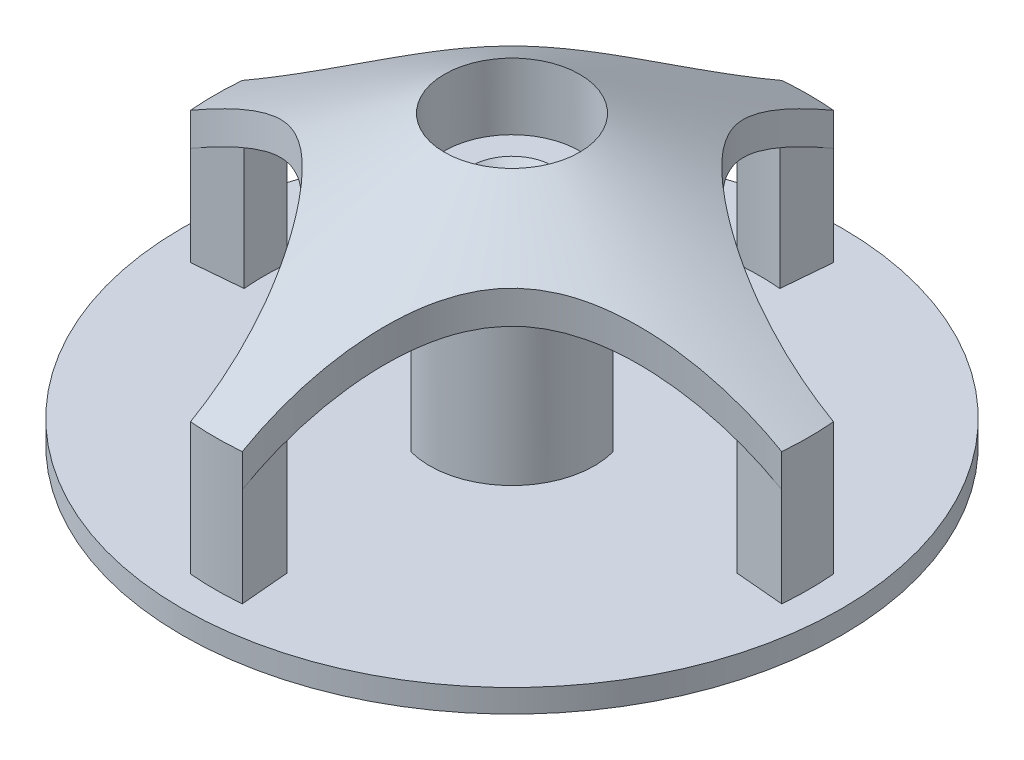
SolidWorks part; units mm, degrees
ref_plane "Front Plane" through (0, 0, 0) normal (0, 0, 1) x (1, 0, 0)
ref_plane "Top Plane" through (0, 0, 0) normal (0, 1, 0) x (1, 0, 0)
ref_plane "Right Plane" through (0, 0, 0) normal (1, 0, 0) x (0, 0, -1)
sketch "Sketch1" plane through (0, 0, 0) normal (0, 1, 0) x (1, 0, 0)
  circle A0 centre (0, 0) radius 127
  dimension "D1" = 254
extrude "Base of base" add sketch "Sketch1" along normal blind 8.89
ref_plane "Top Platform Offset" through (0, 46.99, 0) normal (0, 1, 0) x (1, 0, 0)
sketch "Sketch15" plane through (0, 0, 0) normal (1, 0, 0) x (0, 0, -1)
  line L0 (0, 8.89) -> (0, 44.378) construction
  line L2 (127, 8.89) -> (-127, 8.89) construction
sketch "Sketch7" plane through (0, 0, 0) normal (1, 0, 0) x (0, 0, -1)
  line L1 (127, 8.89) -> (-127, 8.89)
  line L2 (-114.3, 46.99) -> (0, 46.99) construction
  line L3 (-114.3, 46.99) -> (0, 112.9811)
  line L4 (-114.3, 46.99) -> (-114.3, 59.69)
  line L5 (-114.3, 59.69) -> (0, 125.6811)
  line L6 (0, 125.6811) -> (0, 112.9811)
  point P8 (0, 8.89)
  dimension "D1" = 30
  dimension "D2" = 114.3
  dimension "D3" = 38.1
revolve "Top Part of Base" add sketch "Sketch7" angle 360 about L0 region at (0, 86.3356, 57.15)
ref_plane "Offset Plane for Cuts" through (0, 125.6811, 0) normal (0, 1, 0) x (1, 0, 0)
sketch "Sketch8" plane through (0, 125.6811, 0) normal (0, 1, 0) x (1, 0, 0)
  circle A0 centre (0, 0) radius 26.035
  dimension "D1" = 52.07
extrude "Ball Bearing Cut" cut sketch "Sketch8" against normal up to surface (27.7313 mm away)
sketch "Sketch10" plane through (0, 8.89, 0) normal (0, 1, 0) x (1, 0, 0)
  line L0 (0, 0) -> (0, 114.3) construction
  line L1 (0, 0) -> (9.9619, 113.8651)
  line L2 (0, 0) -> (-9.9619, 113.8651)
  circle A0 centre (0, 0) radius 114.3 construction
  circle A1 centre (0, 0) radius 114.3
  circle A2 centre (0, 0) radius 95.25
  arc A3 (9.9619, 113.8651) -> (-9.9619, 113.8651) centre (0, 0) ccw
  dimension "D1" = 190.5
  dimension "D2" = 5
extrude "Support" add sketch "Sketch10" along normal up to surface (49.0985 mm away) contours A2 L0 A3 L2 | L0 A2 L1 A1 region at (-4.5814, 8.89, -104.9303) region at (4.5814, 8.89, -104.9303) up to face at (0, 97.9498, -26.035)
pattern_circular "Supports" count 4 every 90 about axis through (0, 8.89, 0) along (0, 1, 0) of "Support"
sketch "Sketch12" plane through (0, 125.6811, 0) normal (0, 1, 0) x (1, 0, 0)
  arc A4 (9.9619, 113.8651) -> (113.8651, 9.9619) centre (113.8651, 113.8651) ccw
  arc A9 (-9.9619, 113.8651) -> (-113.8651, 9.9619) centre (-113.8651, 113.8651) cw
  arc A10 (-113.8651, -9.9619) -> (-9.9619, -113.8651) centre (-113.8651, -113.8651) cw
  arc A11 (9.9619, -113.8651) -> (113.8651, -9.9619) centre (113.8651, -113.8651) cw
  arc A12 (-113.8651, -9.9619) -> (-9.9619, -113.8651) centre (0, 0) ccw
  arc A13 (113.8651, 9.9619) -> (9.9619, 113.8651) centre (0, 0) ccw
  arc A14 (-9.9619, 113.8651) -> (-113.8651, 9.9619) centre (0, 0) ccw
  arc A15 (9.9619, -113.8651) -> (113.8651, -9.9619) centre (0, 0) ccw
extrude "Cut for Printabiity" cut sketch "Sketch12" against normal up to surface (78.6911 mm away) contours A10 A12 | A9 A14 | A4 A13 | A11 A15 region at (60.8149, 125.6811, -60.8149) region at (-60.8149, 125.6811, -60.8149) region at (-60.8149, 125.6811, 60.8149) region at (60.8149, 125.6811, 60.8149) up to face at (0, 52.4893, 0)
sketch "Reference for height of base" plane through (0, 0, 0) normal (0, 0, 1) x (1, 0, 0)
  line L0 (-26.035, 97.9498) -> (26.035, 97.9498) construction
  line L1 (-26.035, 97.9498) -> (26.035, 97.9498)
  line L2 (26.035, 97.9498) -> (26.035, 8.89) construction
  line L3 (127, 8.89) -> (-127, 8.89) construction
  line L4 (-26.035, 110.6498) -> (26.035, 110.6498) construction
  line L5 (-26.035, 110.6498) -> (26.035, 110.6498)
  line L6 (26.035, 110.6498) -> (26.035, 97.9498) construction
  dimension "D1" = 89.0598
  dimension "D2" = 101.7598
  dimension "D3" = 12.7
sketch "Sketch14" plane through (0, 8.89, 0) normal (0, 1, 0) x (1, 0, 0)
  circle A1 centre (0, 0) radius 13.335
  circle A2 centre (0, 0) radius 26.035 construction
  circle A3 centre (0, 0) radius 26.035
  circle A4 centre (0, 0) radius 31.75
  dimension "D1" = 26.67
  dimension "D3" = 63.5
extrude "Holder for Shoulder" add sketch "Sketch14" along normal blind 76.2 contours A3 A1 region at (-25.2986, 8.89, 0)
extrude "Center Cylinder" add sketch "Sketch14<3>" along normal up to surface (85.7603 mm away) contours A4 A3 region at (-30.852, 8.89, 0) up to face at (0, 97.9498, -26.035)
sketch "Sketch14<3>" plane through (0, 8.89, 0) normal (0, 1, 0) x (1, 0, 0) same geometry as "Sketch14"
chamfer "Funnel into Snap in Place" distance 2.54 angle 45 1 edges at (0, 85.09, 13.335)
ref_plane "Plane for Accessibility Cut" through (-61.9135, 0, 61.9135) normal (0.7071, 0, -0.7071) x (-0.7071, 0, -0.7071)
sketch "Sketch19" plane through (-61.9135, 0, 61.9135) normal (0.7071, 0, -0.7071) x (-0.7071, 0, -0.7071)
  line L0 (31.75, 8.89) -> (-31.75, 8.89) construction
  line L1 (31.75, 8.89) -> (-31.75, 8.89)
  line L2 (0, 8.89) -> (0, 44.378) construction
  line L3 (15.875, 8.89) -> (-15.875, 8.89)
  line L4 (15.875, 8.89) -> (15.875, 59.69)
  line L5 (15.875, 59.69) -> (-15.875, 59.69)
  line L6 (-15.875, 8.89) -> (-15.875, 59.69)
  line L7 (0, 8.89) -> (0, 44.378)
  line L8 (0, 59.69) -> (-15.875, 43.815)
  line L9 (0, 59.69) -> (15.875, 43.815)
  dimension "D1" = 31.75
  dimension "D2" = 15.875
  dimension "D3" = 15.875
  dimension "D4" = 50.8
  dimension "D5" = 45
  dimension "D6" = 45
extrude "Accessibility Cut" cut sketch "Sketch19" along normal through all contours L9 L8 L6 L3 L1 L4 region at (-67.5261, 9.4891, 56.3008)
sketch "Sketch20" plane through (0, 0, 0) normal (1, 0, 0) x (0, 0, -1)
  line L0 (-13.335, 82.55) -> (13.335, 82.55) construction
  line L1 (-13.335, 82.55) -> (13.335, 82.55)
  line L2 (13.335, 82.55) -> (13.335, 88.2939) construction
  line L3 (13.335, 79.375) -> (15.875, 79.375)
  line L4 (15.875, 79.375) -> (13.335, 74.295)
  line L5 (13.335, 74.295) -> (13.335, 79.375)
  dimension "D1" = 3.175
  dimension "D2" = 5.08
  dimension "D3" = 2.54
revolve "Cut-Revolve1" cut sketch "Sketch20" angle 360 about L0 region at (0, 77.6817, -14.1817)
sketch "Sketch21" plane through (0, 0, 0) normal (0, 0, 1) x (1, 0, 0)
  line L0 (-26.035, 110.6498) -> (26.035, 110.6498) construction
  line L1 (13.335, 74.295) -> (-13.335, 74.295) construction
  line L2 (-15.875, 79.375) -> (15.875, 79.375) construction
  line L3 (-26.035, 110.6498) -> (26.035, 110.6498)
  line L4 (13.335, 74.295) -> (-13.335, 74.295)
  line L5 (-15.875, 79.375) -> (15.875, 79.375)
  line L6 (13.335, 82.55) -> (-13.335, 82.55) construction
  line L7 (13.335, 82.55) -> (-13.335, 82.55)
  line L8 (13.335, 82.55) -> (13.335, 79.375) construction
  line L9 (13.335, 79.375) -> (15.875, 79.375) construction
  dimension "D1" = 31.2748
  dimension "D2" = 36.3548
  dimension "D3" = 5.08
  dimension "D4" = 2.54
